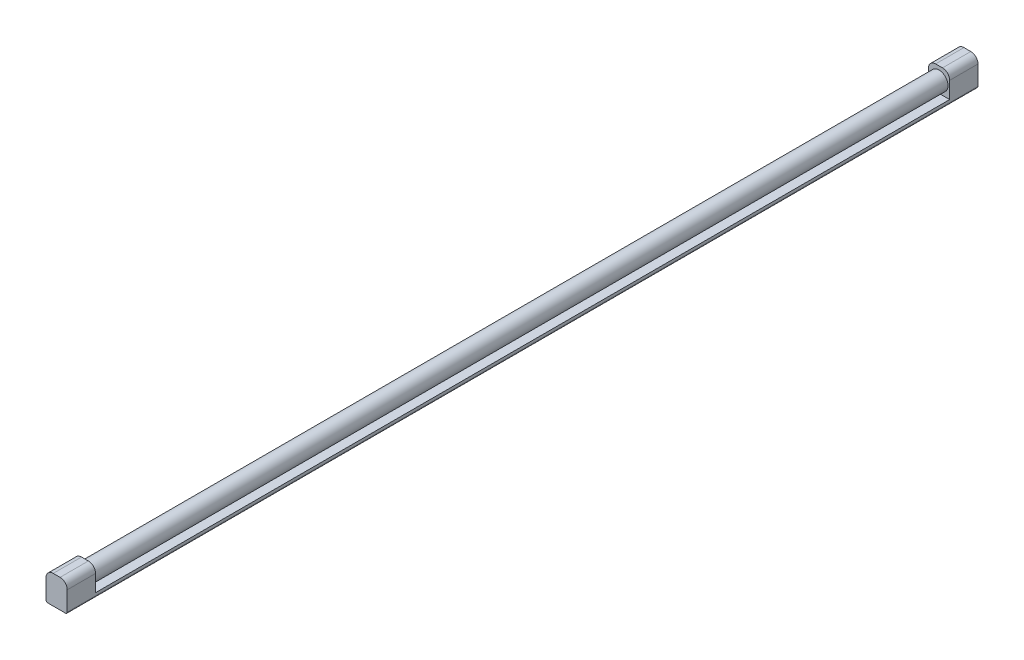
SolidWorks part; units mm, degrees
material "C-Glass Fiber"
ref_plane "Front Plane" through (0, 0, 0) normal (0, 0, 1) x (1, 0, 0)
ref_plane "Top Plane" through (0, 0, 0) normal (0, 1, 0) x (1, 0, 0)
ref_plane "Right Plane" through (0, 0, 0) normal (1, 0, 0) x (0, 0, -1)
sketch "Sketch1" plane through (0, 0, 0) normal (0, 0, 1) x (1, 0, 0)
  line L1 (0, 0) -> (30, 0)
  line L2 (0, 0) -> (0, 40)
  line L3 (0, 40) -> (30, 40)
  line L4 (30, 0) -> (30, 40)
  dimension "D1" = 30
  dimension "D2" = 40
extrude "Boss-Extrude1" add sketch "Sketch1" along normal blind 40
fillet "Fillet1" radius 10.16 2 edges at (30, 40, 20) (0, 40, 20)
fillet "Fillet2" radius 2.54 2 edges at (0, 0, 20) (30, 0, 20)
sketch "Sketch3" plane through (0, 0, 40) normal (0, 0, 1) x (1, 0, 0)
  line L0 (15, 40) -> (15, 15.2957) construction
  line L1 (19.84, 40) -> (10.16, 40) construction
  circle A0 centre (15, 22.22) radius 12.7
  dimension "D1" = 25.4
  dimension "D2" = 17.78
extrude "Boss-Extrude2" add sketch "Sketch3" along normal blind 1206
sketch "Sketch6" plane through (0, 0, 1246) normal (0, 0, 1) x (1, 0, 0)
  line L1 (0, 0) -> (30, 0)
  line L2 (0, 0) -> (0, 40)
  line L3 (0, 40) -> (30, 40)
  line L4 (30, 0) -> (30, 40)
extrude "Boss-Extrude3" add sketch "Sketch6" along normal blind 40
fillet "Fillet3" radius 10.16 2 edges at (30, 40, 1266) (0, 40, 1266)
fillet "Fillet4" radius 2.54 2 edges at (0, 0, 1266) (30, 0, 1266)
sketch "Sketch7" plane through (0, 0, 40) normal (0, 0, 1) x (1, 0, 0)
  line L0 (30, 2.54) -> (30, 29.84) construction
  line L1 (0, 0) -> (30, 0)
  line L2 (0, 0) -> (0, 6.35)
  line L3 (0, 6.35) -> (30, 6.35)
  line L4 (30, 0) -> (30, 6.35)
  dimension "D1" = 6.35
extrude "Boss-Extrude4" add sketch "Sketch7" along direction (0, 0, -1) on the side of the normal up to surface (1206 mm away) up to face at (27.7, 22.22, 1246)
fillet "Fillet5" radius 2.54 2 edges at (30, 0, 643) (0, 0, 643)
